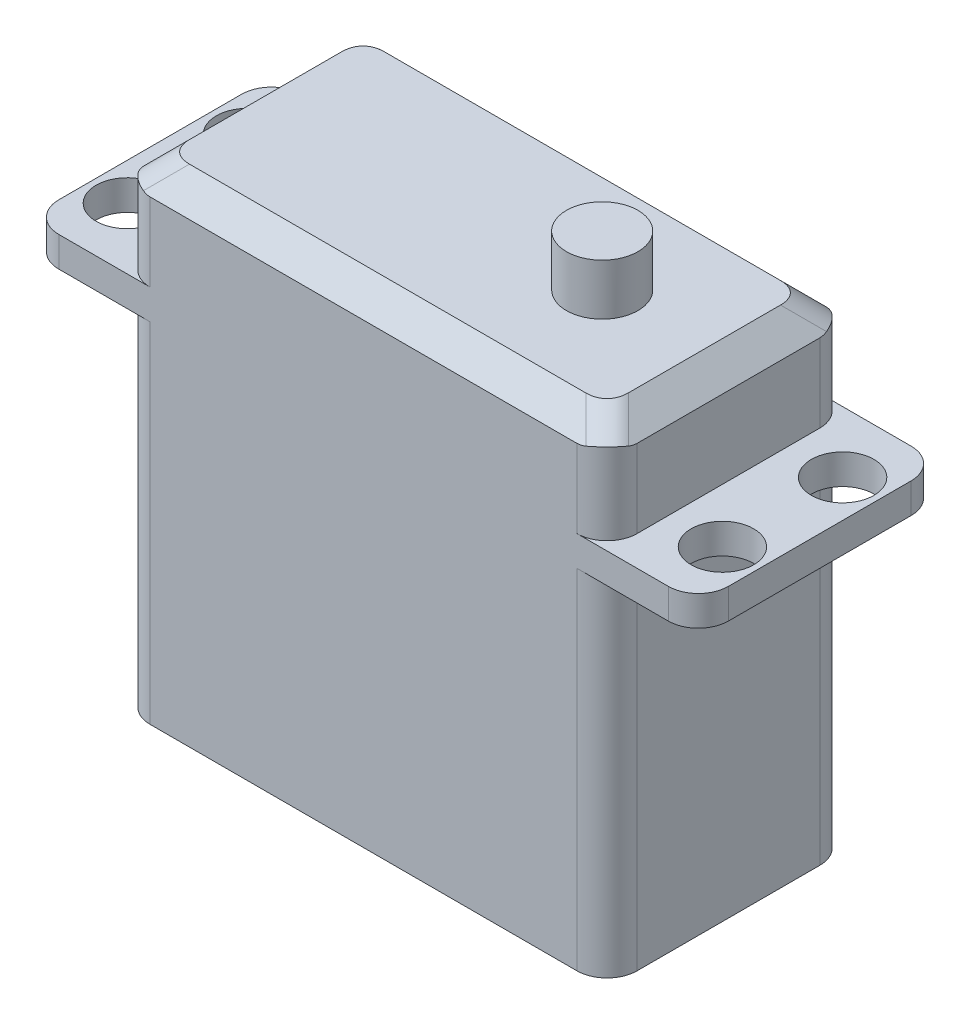
SolidWorks part; units mm, degrees
ref_plane "Front Plane" through (0, 0, 0) normal (0, 0, 1) x (1, 0, 0)
ref_plane "Top Plane" through (0, 0, 0) normal (0, 1, 0) x (1, 0, 0)
ref_plane "Right Plane" through (0, 0, 0) normal (1, 0, 0) x (0, 0, -1)
sketch "Sketch1" plane through (0, 0, 0) normal (0, 0, 1) x (1, 0, 0)
  line L0 (-20.25, 0) -> (20.25, 0)
  line L1 (20.25, 0) -> (20.25, 29)
  line L2 (20.25, 29) -> (27.85, 29)
  line L3 (27.85, 29) -> (27.85, 31.5)
  line L4 (27.85, 31.5) -> (20.25, 31.5)
  line L5 (-20.25, 0) -> (-20.25, 29)
  line L6 (-20.25, 29) -> (-27.85, 29)
  line L7 (-27.85, 29) -> (-27.85, 31.5)
  line L8 (-27.85, 31.5) -> (-20.25, 31.5)
  line L9 (-20.25, 31.5) -> (-20.25, 40)
  line L10 (-20.25, 40) -> (20.25, 40)
  line L11 (20.25, 40) -> (20.25, 31.5)
  point P4 (0, 0)
  dimension "D1" = 29
  dimension "D2" = 29
  dimension "D3" = 2.5
  dimension "D4" = 2.5
  dimension "D5" = 40
  dimension "D6" = 40.5
  dimension "D7" = 55.7
extrude "Boss-Extrude1" add sketch "Sketch1" along normal blind 20.2
ref_plane "Plane1" through (0, 40, 0) normal (0, 1, 0) x (1, 0, 0)
sketch "Sketch2" plane through (0, 40, 0) normal (0, 1, 0) x (1, 0, 0)
  line L0 (-20.25, -10.1) -> (9.75, -10.1) construction
  line L1 (-20.25, -20.2) -> (-20.25, 0) construction
  circle A0 centre (9.75, -10.1) radius 2.975
  dimension "D2" = 5.95
  dimension "D1" = 30
extrude "Boss-Extrude2" add sketch "Sketch2" along normal blind 4.25
sketch "Sketch3" plane through (0, 0, 0) normal (0, 1, 0) x (1, 0, 0)
  line L0 (-20.25, -15.1) -> (-20.25, -5.1) construction
  line L1 (-20.25, -10.1) -> (-20.25, 0) construction
  line L2 (-20.25, -20.2) -> (-20.25, 0) construction
  line L3 (-20.25, -5.1) -> (-24.75, -5.1) construction
  line L4 (-20.25, -15.1) -> (-24.75, -15.1) construction
  circle A0 centre (-24.75, -5.1) radius 2.6
  circle A1 centre (-24.75, -15.1) radius 2.6
  point P3 (-20.25, -10.1)
  dimension "D1" = 10.1
  dimension "D2" = 10
extrude "Cut-Extrude1" cut sketch "Sketch3" along normal blind 4.25 from offset 29
mirror "Mirror1" about plane through (0, 0, 0) normal (1, 0, 0) of "Cut-Extrude1"
chamfer "Chamfer1" distance 2 4 edges at (0, 40, 20.2) (20.25, 40, 10.1) (0, 40, 0) (-20.25, 40, 10.1)
fillet "Fillet1" radius 2.5 16 edges at (19.25, 39, 1) (19.25, 39, 19.2) (-19.25, 39, 19.2) (-19.25, 39, 1) (20.25, 14.5, 20.2) (20.25, 14.5, 0) (27.85, 30.25, 20.2) (27.85, 30.25, 0) (20.25, 34.75, 0) (20.25, 34.75, 20.2) (-20.25, 14.5, 0) (-20.25, 14.5, 20.2) (-27.85, 30.25, 20.2) (-27.85, 30.25, 0) (-20.25, 34.75, 0) (-20.25, 34.75, 20.2)
